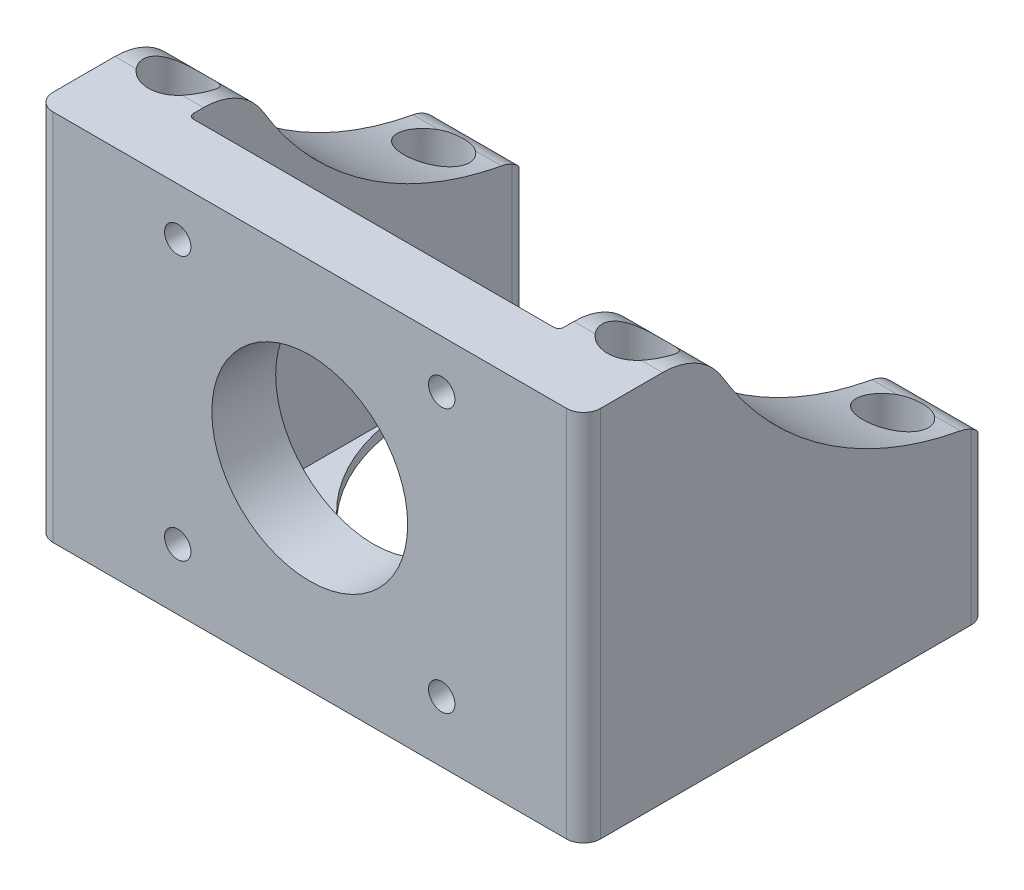
SolidWorks part; units mm, degrees
note: The reader was unsure of these and kept them because the rebuilt part matched: shared geometry of "Sketch5<3>".
ref_plane "Front Plane" through (0, 0, 0) normal (0, 0, 1) x (1, 0, 0)
ref_plane "Top Plane" through (0, 0, 0) normal (0, 1, 0) x (1, 0, 0)
ref_plane "Right Plane" through (0, 0, 0) normal (1, 0, 0) x (0, 0, -1)
sketch "Sketch1" plane through (0, 0, 0) normal (0, 0, 1) x (1, 0, 0)
  line L0 (0, 0) -> (0, 36.6282) construction
  line L1 (0, 0) -> (42.2877, 0) construction
  line L2 (0, 0) -> (32.6841, 32.6841) construction
  line L3 (0, 21.15) -> (21.15, 21.15)
  line L4 (21.15, 0) -> (21.15, 21.15)
  line L5 (0, 15.5) -> (15.5, 15.5) construction
  line L6 (15.5, 15.5) -> (15.5, 0) construction
  line L7 (21.15, 0) -> (21.15, -21.15)
  line L8 (0, -21.15) -> (21.15, -21.15)
  line L9 (15.5, 0) -> (15.5, -15.5) construction
  line L10 (15.5, -15.5) -> (0, -15.5) construction
  line L11 (0, -21.15) -> (-21.15, -21.15)
  line L12 (-21.15, 0) -> (-21.15, -21.15)
  line L13 (0, -15.5) -> (-15.5, -15.5) construction
  line L14 (-15.5, -15.5) -> (-15.5, 0) construction
  line L15 (-21.15, 0) -> (-21.15, 21.15)
  line L16 (0, 21.15) -> (-21.15, 21.15)
  line L17 (-15.5, 0) -> (-15.5, 15.5) construction
  line L18 (-15.5, 15.5) -> (0, 15.5) construction
  circle A0 centre (15.5, 15.5) radius 1.55
  circle A1 centre (15.5, -15.5) radius 1.55
  circle A2 centre (-15.5, -15.5) radius 1.55
  circle A3 centre (-15.5, 15.5) radius 1.55
  circle A4 centre (0, 0) radius 11.5
  point P36 (0, 0)
  dimension "D3" = 3.1
  dimension "D5" = 23
  dimension "D1" = 15.5
  dimension "D2" = 21.15
  dimension "D4" = 4
extrude "Boss-Extrude1" add sketch "Sketch1" along normal blind 7.5
sketch "Sketch2" plane through (-21.15, 0, 0) normal (-1, 0, 0) x (0, 0, 1)
  line L0 (7.5, 21.15) -> (-1.7717, 21.15)
  line L1 (7.5, -21.15) -> (-40, -21.15)
  line L2 (0, 21.15) -> (0, -21.15) construction
  line L3 (-40, -21.15) -> (-40, -6.15)
  line L8 (0, 21.15) -> (0, -21.15)
  line L9 (0, -21.15) -> (7.5, -21.15)
  line L10 (7.5, -21.15) -> (7.5, 21.15)
  line L11 (7.5, 21.15) -> (0, 21.15)
  line L12 (0, 21.15) -> (0, -21.15)
  line L13 (0, -21.15) -> (7.5, -21.15)
  line L15 (7.5, 21.15) -> (0, 21.15)
  arc A0 (-40, -6.15) -> (-36.7684, -2.2727) centre (-36.0582, -6.15) cw
  arc A1 (-1.7717, 21.15) -> (-8.8257, 17.1424) centre (-1.7717, 12.9382) ccw
  arc A2 (-8.8257, 17.1424) -> (-36.7684, -2.2727) centre (-44.185, 38.217) cw
  line M3 (0, 21.15) -> (0, -21.15)
  line M4 (0, -21.15) -> (7.5, -21.15)
  line M5 (7.5, -21.15) -> (7.5, 21.15)
  line M6 (7.5, 21.15) -> (0, 21.15)
  dimension "D1" = 40
  dimension "D2" = 15
  dimension "D3" = 0
extrude "Boss-Extrude2" add sketch "Sketch2" along normal blind 11 contours M6 M3 M4 M5 | A1 A2 A0 L3 L1 L0 M3
sketch "Sketch3" plane through (0, 21.15, 0) normal (0, 1, 0) x (1, 0, 0)
  line L0 (-21.75, 0.6) -> (-21.75, 41.9381)
  line L1 (21.15, 0) -> (-21.15, 0) construction
  line L2 (-21.15, 1.7717) -> (-21.15, 8.8257) construction
  line L3 (-21.75, 41.9381) -> (-16.9322, 41.9381)
  line L4 (-16.9322, 41.9381) -> (-16.9322, 2.9783)
  line L5 (-16.9322, 2.9783) -> (-21.15, 0)
  arc A0 (-21.15, 0) -> (-21.75, 0.6) centre (-21.15, 0.6) cw
  dimension "D1" = 0.6
extrude "Cut-Extrude1" cut sketch "Sketch3" against normal through all both and the other way through all
mirror "Mirror1" about plane through (0, 0, 0) normal (1, 0, 0) of "Boss-Extrude2", "Cut-Extrude1"
sketch "Sketch4" plane through (0, -21.15, 0) normal (0, -1, 0) x (1, 0, 0)
  line L8 (21.75, -0.6) -> (21.75, -40)
  line L9 (21.75, -40) -> (32.15, -40)
  line L10 (32.15, -40) -> (32.15, 7.5)
  line L11 (32.15, 7.5) -> (-32.15, 7.5)
  line L12 (-32.15, 7.5) -> (-32.15, -40)
  line L13 (-32.15, -40) -> (-21.75, -40)
  line L14 (-21.75, -40) -> (-21.75, -0.6)
  line L15 (-21.15, 0) -> (21.15, 0)
  line L16 (21.75, -0.6) -> (21.75, -40)
  line L17 (21.75, -40) -> (32.15, -40)
  line L18 (32.15, -40) -> (32.15, 7.5)
  line L19 (32.15, 7.5) -> (-32.15, 7.5)
  line L20 (-32.15, 7.5) -> (-32.15, -40)
  line L21 (-32.15, -40) -> (-21.75, -40)
  line L22 (-21.75, -40) -> (-21.75, -0.6)
  line L23 (-21.15, 0) -> (21.15, 0)
  arc A2 (21.75, -0.6) -> (21.15, 0) centre (21.15, -0.6) ccw
  arc A3 (-21.15, 0) -> (-21.75, -0.6) centre (-21.15, -0.6) ccw
  arc A4 (21.75, -0.6) -> (21.15, 0) centre (21.15, -0.6) ccw
  arc A5 (-21.15, 0) -> (-21.75, -0.6) centre (-21.15, -0.6) ccw
  dimension "D1" = 0
extrude "Boss-Extrude3" add sketch "Sketch4" along normal blind 1.5
sketch "Sketch5" plane through (0, -22.65, 0) normal (0, -1, 0) x (1, 0, 0)
  line L0 (0, 0) -> (-32.15, 0) construction
  line L1 (-32.15, 7.5) -> (-32.15, -40) construction
  line L2 (-26.95, 0) -> (-26.95, -40) construction
  line L3 (-32.15, -40) -> (-21.75, -40) construction
  line L4 (0, 0) -> (0, -31.6298) construction
  circle A0 centre (-26.95, -4) radius 3.5
  circle A1 centre (-26.95, -34) radius 3.5
  circle A2 centre (-26.95, -4) radius 1.5
  circle A3 centre (-26.95, -34) radius 1.5
  circle A4 centre (26.95, -34) radius 1.5
  circle A5 centre (26.95, -4) radius 1.5
  circle A6 centre (26.95, -34) radius 3.5
  circle A7 centre (26.95, -4) radius 3.5
  dimension "D3" = 7
  dimension "D4" = 3
  dimension "D1" = 4
  dimension "D2" = 6
extrude "Cut-Extrude2" cut sketch "Sketch5" against normal through all both and the other way through all contours A2 | A3 | A4 | A5
extrude "Cut-Extrude3" cut sketch "Sketch5<3>" against normal blind 47.5 from offset 15 contours A1 A3 | A0 | A7 | A6 offset against normal yes
sketch "Sketch5<3>" plane through (0, -22.65, 0) normal (0, -1, 0) x (1, 0, 0) same geometry as "Sketch5"
fillet "Fillet2" radius 2 6 edges at (-21.75, -14.4, -40) (32.15, -14.4, -40) (21.75, -14.4, -40) (-32.15, -14.4, -40) (32.15, -0.75, 7.5) (-32.15, -0.75, 7.5)
sketch "Sketch6" plane through (0, -22.65, 0) normal (0, -1, 0) x (1, 0, 0)
  line L0 (-30.15, -40) -> (-23.75, -40) construction
  line L1 (24.2949, 1.7498) -> (-24.4921, 1.7498)
  line L2 (24.2949, 1.7498) -> (24.2949, -40)
  line L3 (24.2949, -40) -> (-24.4921, -40)
  line L4 (-24.4921, 1.7498) -> (-24.4921, -40)
extrude "Boss-Extrude4" add sketch "Sketch6" against normal blind 1.2
sketch "Sketch7" plane through (0, -21.45, 0) normal (0, 1, 0) x (1, 0, 0)
  line L0 (21.75, 36.7684) -> (21.75, 8.8257) construction
  line L1 (21.75, 38) -> (21.75, 36.7684) construction
  line L2 (-21.75, 8.8257) -> (-21.75, 36.7684) construction
  line L3 (-21.75, 36.7684) -> (-21.75, 38) construction
  line L4 (21.75, 36.7684) -> (21.75, 26.4016)
  line L5 (21.75, 38) -> (21.75, 36.7684)
  line L6 (-21.75, 26.4016) -> (-21.75, 36.7684)
  line L7 (-21.75, 36.7684) -> (-21.75, 38)
  line L8 (0, 0) -> (0, 34.2235) construction
  line L9 (0, 4.6516) -> (-13.9295, 4.6516) construction
  line L10 (-23.75, 40) -> (-23.75, 46.1873)
  line L11 (-23.75, 46.1873) -> (23.75, 46.1873)
  line L12 (23.75, 46.1873) -> (23.75, 40)
  arc A0 (23.75, 40) -> (21.75, 38) centre (23.75, 38) ccw construction
  arc A1 (-21.75, 38) -> (-23.75, 40) centre (-23.75, 38) ccw construction
  arc A2 (23.75, 40) -> (21.75, 38) centre (23.75, 38) ccw
  arc A3 (-21.75, 38) -> (-23.75, 40) centre (-23.75, 38) ccw
  arc A4 (-21.75, 26.4016) -> (21.75, 26.4016) centre (0, 26.4016) ccw
extrude "Cut-Extrude4" cut sketch "Sketch7" against normal through all
